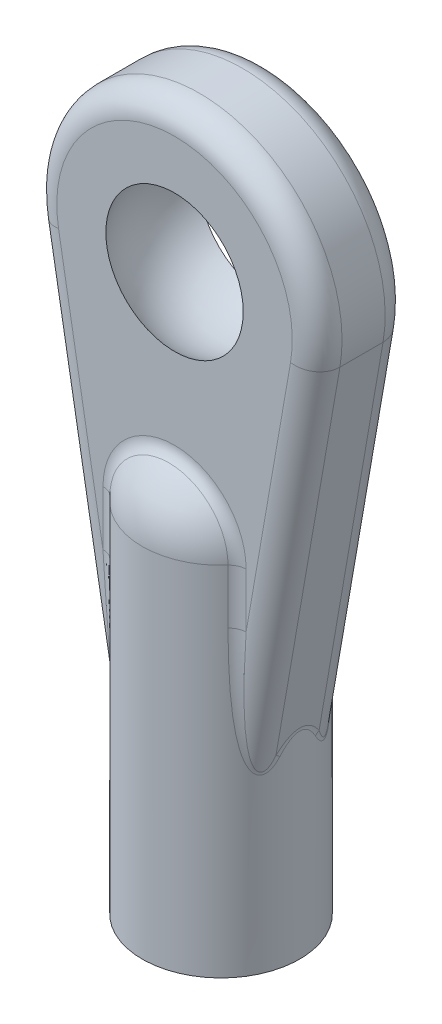
SolidWorks part; units mm, degrees
material "Acrylic (Medium-high impact)"
ref_plane "Front Plane" through (0, 0, 0) normal (0, 0, 1) x (1, 0, 0)
ref_plane "Top Plane" through (0, 0, 0) normal (0, 1, 0) x (1, 0, 0)
ref_plane "Right Plane" through (0, 0, 0) normal (1, 0, 0) x (0, 0, -1)
sketch "Sketch1" plane through (0, 0, 0) normal (0, 0, 1) x (1, 0, 0)
  line L0 (0, 0) -> (0, -17.45) construction
  line L1 (0, -17.45) -> (-2.375, -17.45) construction
  line L2 (-2.375, -17.45) -> (-2.375, -11.45) construction
  line L3 (-2.375, -11.45) -> (2.375, -11.45) construction
  line L4 (2.375, -11.45) -> (2.375, -17.45) construction
  line L5 (2.375, -17.45) -> (0, -17.45) construction
  line L6 (0, 0) -> (0, 4.3) construction
  line L7 (2.375, -11.45) -> (4.2365, -0.7361)
  line L8 (-4.2365, -0.7361) -> (-2.375, -11.45)
  line L9 (-2.375, -11.45) -> (2.375, -11.45) construction
  line L10 (-2.375, -11.45) -> (-2.2013, -12.45)
  line L11 (-2.2013, -12.45) -> (2.2013, -12.45)
  line L12 (2.2013, -12.45) -> (2.375, -11.45)
  arc A0 (4.2365, -0.7361) -> (-4.2365, -0.7361) centre (0, 0) ccw
  dimension "D1" = 8.6
  dimension "D2" = 4.75
  dimension "D3" = 21.75
  dimension "D4" = 6
  dimension "D5" = 1
extrude "Boss-Extrude1" add sketch "Sketch1" along normal mid plane 2.8
sketch "Sketch2" plane through (0, 0, 0) normal (0, 0, 1) x (1, 0, 0)
  line L0 (0, 0) -> (0, -17.45) construction
  line L1 (0, -17.45) -> (-2.375, -17.45)
  line L2 (-2.375, -17.45) -> (-2.375, -11.45)
  line L3 (-2.375, -11.45) -> (-2.375, -6.675)
  line L4 (0, -6.675) -> (0, -4.3)
  line L5 (0, -6.675) -> (0, -17.45)
  line L6 (2.375, -17.45) -> (0, -17.45) construction
  circle A0 centre (0, 0) radius 4.3 construction
  arc A1 (4.2365, -0.7361) -> (-4.2365, -0.7361) centre (0, 0) ccw construction
  arc A2 (0, -4.3) -> (-2.375, -6.675) centre (0, -6.675) ccw
revolve "Revolve1" add sketch "Sketch2" angle 360 about L0
sketch "Sketch3" plane through (0, 0, 0) normal (1, 0, 0) x (0, 0, -1)
  line L0 (0, -2.5) -> (0, 2.5)
  arc A0 (0, 2.5) -> (0, -2.5) centre (0, 0) ccw
  dimension "D1" = 2.5
revolve "Cut-Revolve1" cut sketch "Sketch3" angle 360 about L0
fillet "Fillet1" radius 0.75 6 edges at (3.2189, -6.593, -1.4) (0, 4.3, -1.4) (3.2189, -6.593, 1.4) (0, 4.3, 1.4) (-3.2189, -6.593, -1.4) (-3.2189, -6.593, 1.4)
fillet "Fillet2" radius 0.5 6 edges at (1.9185, -8.1856, -1.4) (0, -4.7565, -1.4) (1.9185, -8.1856, 1.4) (0, -4.7565, 1.4) (-1.9185, -8.1856, -1.4) (-1.9185, -8.1856, 1.4)
hole_wizard "M3 Tapped Hole1" positions "Sketch4" profile "Sketch5" tap size "M3" standard "DIN"
sketch "Sketch4" plane through (0, -17.45, 0) normal (0, -1, 0) x (-1, 0, 0)
  point P0 (0, 0)
cosmetic thread "Hole Thread1" parameters "D1"=6.096, "D2"=3
sketch "Sketch5" plane through (0, -17.45, 0) normal (1, 0, 0) x (0, 0, -1)
  line L0 (0, 0) -> (0, 9.3871)
  line L1 (0, 9.3871) -> (1.25, 8.636)
  line L2 (1.25, 8.636) -> (1.25, 0)
  line L5 (1.25, 0) -> (0, 0)
  line L10 (0, 9.3871) -> (-1.25, 8.636) construction
  line L11 (0, -6.35) -> (0, 107.95) construction
  dimension "Tap Drill Dia." = 2.5
  dimension "Tap Drill Depth" = 8.636
  dimension "Drill Angle" = 118
